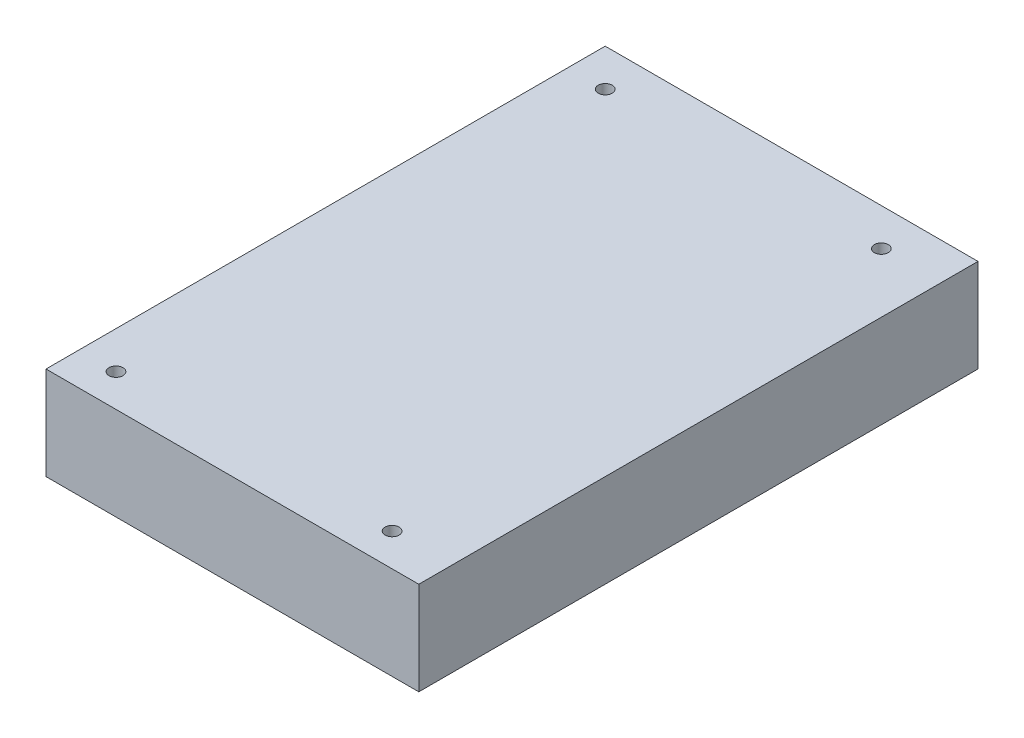
SolidWorks part; units mm, degrees
ref_plane "Front Plane" through (0, 0, 0) normal (0, 0, 1) x (1, 0, 0)
ref_plane "Top Plane" through (0, 0, 0) normal (0, 1, 0) x (1, 0, 0)
ref_plane "Right Plane" through (0, 0, 0) normal (1, 0, 0) x (0, 0, -1)
sketch "Sketch1" plane through (0, 0, 0) normal (0, 1, 0) x (1, 0, 0)
  line L1 (-35.5322, 92.023) -> (66.0678, 92.023)
  line L2 (-35.5322, 92.023) -> (-35.5322, -60.377)
  line L3 (-35.5322, -60.377) -> (66.0678, -60.377)
  line L4 (66.0678, 92.023) -> (66.0678, -60.377)
  dimension "D1" = 101.6
  dimension "D2" = 152.4
extrude "Boss-Extrude1" add sketch "Sketch1" along normal blind 25.4
sketch "Sketch2" plane through (0, 25.4, 0) normal (0, 1, 0) x (1, 0, 0)
  line L0 (-35.5322, 92.023) -> (-35.5322, -60.377) construction
  line L1 (66.0678, 92.023) -> (-35.5322, 92.023) construction
  circle A0 centre (-25.3722, 81.863) radius 1.905
  circle A1 centre (49.885, 81.863) radius 1.905
  circle A2 centre (-25.3722, -51.4704) radius 1.905
  circle A3 centre (49.885, -51.4704) radius 1.905
  dimension "D3" = 3.81
  dimension "D1" = 10.16
  dimension "D2" = 10.16
extrude "Cut-Extrude1" cut sketch "Sketch2" against normal blind 25.4
